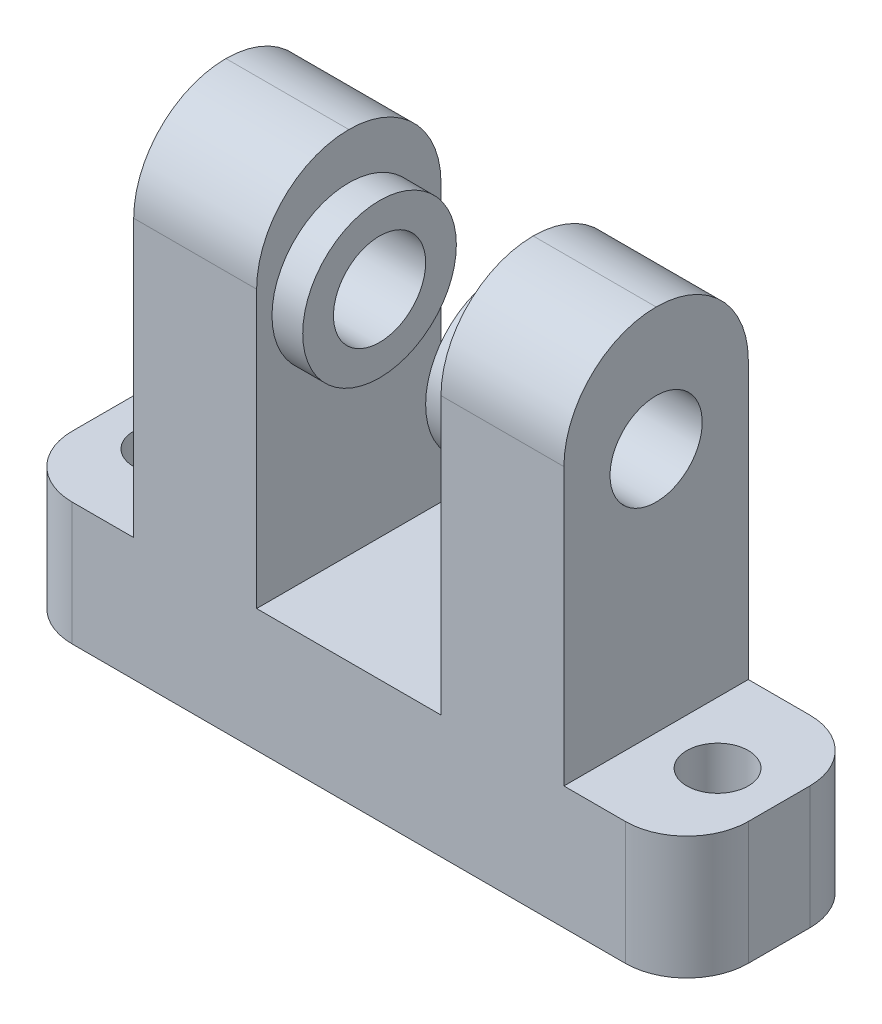
SolidWorks part; units mm, degrees
ref_plane "Front Plane" through (0, 0, 0) normal (0, 0, 1) x (1, 0, 0)
ref_plane "Top Plane" through (0, 0, 0) normal (0, 1, 0) x (1, 0, 0)
ref_plane "Right Plane" through (0, 0, 0) normal (1, 0, 0) x (0, 0, -1)
sketch "Sketch2" plane through (0, 0, 0) normal (0, 1, 0) x (1, 0, 0)
  line L1 (-7, 3) -> (7, 3)
  line L2 (-7, 3) -> (-7, -3)
  line L3 (-7, -3) -> (7, -3)
  line L4 (7, 3) -> (7, -3)
  line L5 (-7, 3) -> (7, -3) construction
  line L6 (-7, -3) -> (7, 3) construction
  point P0 (0, 0)
extrude "Boss-Extrude1" add sketch "Sketch2" along normal blind 4
sketch "Sketch3" plane through (0, 4, 0) normal (0, 1, 0) x (1, 0, 0)
  line L0 (-7, -3) -> (-3, -3)
  line L1 (-7, -3) -> (7, -3) construction
  line L2 (-3, -3) -> (-3, 3)
  line L3 (7, 3) -> (-7, 3) construction
  line L4 (-3, 3) -> (-7, 3)
  line L5 (-7, 3) -> (-7, -3)
  line L6 (7, -3) -> (3, -3)
  line L7 (3, -3) -> (3, 3)
  line L8 (3, 3) -> (7, 3)
  line L9 (7, 3) -> (7, -3)
extrude "Boss-Extrude2" add sketch "Sketch3" along normal blind 12
sketch "Sketch4" plane through (7, 0, 0) normal (1, 0, 0) x (0, 0, -1)
  circle A0 centre (0, 12) radius 1.5
extrude "Cut-Extrude1" cut sketch "Sketch4" against normal through all both and the other way through all
sketch "Sketch5" plane through (-3, 0, 0) normal (1, 0, 0) x (0, 0, -1)
  circle A0 centre (0, 12) radius 1.5
  circle A1 centre (0, 12) radius 2.5
extrude "Boss-Extrude3" add sketch "Sketch5" along normal blind 1
sketch "Sketch6" plane through (3, 0, 0) normal (-1, 0, 0) x (0, 0, 1)
  circle A0 centre (0, 12) radius 1.5
  circle A1 centre (0, 12) radius 2.5
extrude "Boss-Extrude4" add sketch "Sketch6" along normal blind 1
sketch "Sketch7" plane through (0, 4, 0) normal (0, 1, 0) x (1, 0, 0)
  line L2 (11, 3) -> (11, -3)
  line L3 (11, -3) -> (7, -3)
  line L4 (-7, -3) -> (-7, 3)
  line L5 (-7, 3) -> (-7, -3) construction
  line L6 (-7, 3) -> (-11, 3)
  line L7 (-11, 3) -> (-11, -3)
  line L8 (-11, -3) -> (-7, -3)
  line L9 (11, 3) -> (7, 3)
  line L10 (7, 3) -> (7, -3)
  circle A0 centre (9, 0) radius 1
  circle A1 centre (-9, 0) radius 1
extrude "Boss-Extrude5" add sketch "Sketch7" against normal blind 4
fillet "Fillet1" radius 2 4 edges at (-11, 2, -3) (-11, 2, 3) (11, 2, 3) (11, 2, -3)
fillet "Fillet2" radius 3 4 edges at (-5, 16, -3) (5, 16, -3) (5, 16, 3) (-5, 16, 3)
